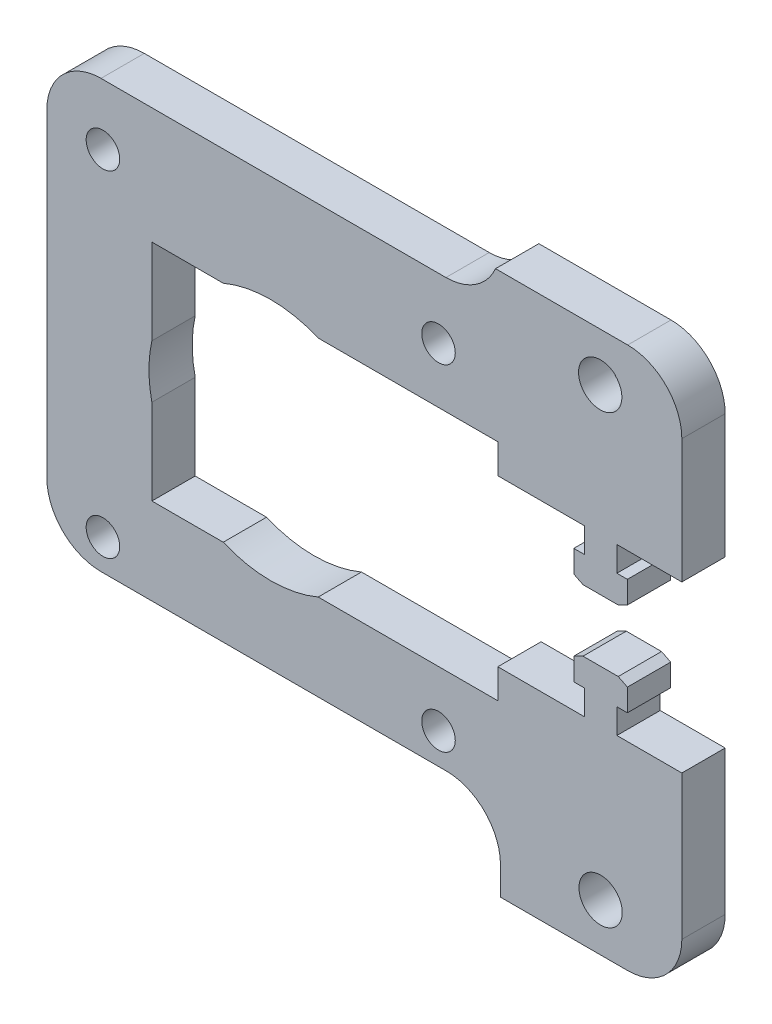
SolidWorks part; units mm, degrees
ref_plane "Front Plane" through (0, 0, 0) normal (0, 0, 1) x (1, 0, 0)
ref_plane "Top Plane" through (0, 0, 0) normal (0, 1, 0) x (1, 0, 0)
ref_plane "Right Plane" through (0, 0, 0) normal (1, 0, 0) x (0, 0, -1)
sketch "Sketch1" plane through (0, 0, 0) normal (0, 0, 1) x (1, 0, 0)
  line L0 (-6.8986, 24.1765) -> (-6.8986, 21.8765)
  line L1 (-6.8986, 21.8765) -> (-14.8986, 21.8765)
  line L2 (-14.8986, 21.8765) -> (-14.8986, 19.1565)
  line L4 (2.1014, 11.1565) -> (2.1014, 21.8765)
  line L7 (-3.8986, 24.1765) -> (-2.9286, 24.1765)
  line L8 (-2.9286, 24.1765) -> (-2.9286, 26.2329)
  line L9 (-2.9286, 26.2329) -> (-3.7758, 26.6565)
  line L10 (-3.7758, 26.6565) -> (-7.0314, 26.6565)
  line L11 (-7.0314, 26.6565) -> (-7.8786, 26.2329)
  line L12 (-7.8786, 26.2329) -> (-7.8786, 24.1765)
  line L13 (-7.8786, 24.1765) -> (-6.8986, 24.1765)
  line L14 (-56.5588, 11.1565) -> (2.1014, 11.1565)
  line L17 (-14.8986, 19.1565) -> (-46.857, 19.1565)
  line L18 (-56.5588, 11.1565) -> (-56.5588, 19.1565)
  line L19 (-3.8986, 24.1765) -> (-3.8986, 21.8765)
  line L20 (-3.8986, 21.8765) -> (2.1014, 21.8765)
  line L21 (2.1014, 29.5165) -> (-53.6577, 29.5165) construction
  line L22 (-7.8786, 34.8565) -> (-6.8986, 34.8565)
  line L23 (-7.8786, 32.8001) -> (-7.8786, 34.8565)
  line L24 (-7.0314, 32.3765) -> (-7.8786, 32.8001)
  line L25 (-3.7758, 32.3765) -> (-7.0314, 32.3765)
  line L26 (-2.9286, 32.8001) -> (-3.7758, 32.3765)
  line L27 (-2.9286, 34.8565) -> (-2.9286, 32.8001)
  line L28 (-3.8986, 37.1565) -> (2.1014, 37.1565)
  line L29 (-3.8986, 34.8565) -> (-3.8986, 37.1565)
  line L30 (-3.8986, 34.8565) -> (-2.9286, 34.8565)
  line L31 (-6.8986, 37.1565) -> (-14.8986, 37.1565)
  line L32 (-6.8986, 34.8565) -> (-6.8986, 37.1565)
  line L33 (-56.5588, 47.8765) -> (-56.5588, 39.8765)
  line L34 (-14.8986, 39.8765) -> (-46.857, 39.8765)
  line L36 (2.1014, 47.8765) -> (2.1014, 37.1565)
  line L37 (-14.8986, 37.1565) -> (-14.8986, 39.8765)
  line L38 (-56.5588, 47.8765) -> (-56.5588, 50.6194)
  line L39 (-56.5588, 50.6194) -> (2.1014, 50.6194)
  line L40 (2.1014, 50.6194) -> (2.1014, 47.8765)
  line L41 (-56.5588, 39.8765) -> (-56.5588, 19.1565)
  line L42 (-46.857, 39.8765) -> (-46.857, 19.1565)
  circle A0 centre (-51.3786, 14.0165) radius 1.55
  circle A1 centre (-20.3786, 14.0165) radius 1.55
  circle A4 centre (-51.3786, 45.0165) radius 1.55
  circle A5 centre (-20.3786, 45.0165) radius 1.55
  dimension "D12" = 3.1
  dimension "D13" = 3.1
  dimension "D14" = 31
  dimension "D16" = 15.5
  dimension "D15" = 15.5
  dimension "D21" = 11.1565
  dimension "D19" = 3.1
  dimension "D23" = 3.1
  dimension "D26" = 31
  dimension "D2" = 2.48
  dimension "D3" = 206.565
  dimension "D4" = 206.565
  dimension "D5" = 4.95
  dimension "D6" = 90
  dimension "D7" = 8
  dimension "D8" = 90
  dimension "D9" = 6
  dimension "D10" = 2.3
  dimension "D11" = 2.86
  dimension "D22" = 2.1014
extrude "Boss-Extrude1" add sketch "Sketch1" along normal blind 4
sketch "Sketch2" plane through (0, 0, 4) normal (0, 0, 1) x (1, 0, 0)
  line L0 (-51.3786, 45.0165) -> (-20.3786, 14.0165) construction
  circle A0 centre (-35.8786, 29.5165) radius 11.25
  dimension "D1" = 22.5
extrude "Cut-Extrude1" cut sketch "Sketch2" against normal blind 10
sketch "Sketch4" plane through (0, 0, 0) normal (0, 0, -1) x (-1, 0, 0)
  line L0 (5.4036, 32.3765) -> (5.4036, 53.6194) construction
  line L2 (-2.1014, 50.6194) -> (-2.1014, 53.6194)
  line L3 (-2.1014, 53.6194) -> (15.1092, 53.6194)
  line L4 (15.1092, 50.6194) -> (15.1092, 53.6194)
  line L6 (-2.1014, 11.1565) -> (-2.1014, 3.5631)
  line L7 (-2.1014, 3.5631) -> (14.6532, 3.5631)
  line L8 (14.6532, 11.1565) -> (14.6532, 3.5631)
  line L9 (7.0314, 32.3765) -> (3.7758, 32.3765) construction
  line L10 (5.4036, 26.6565) -> (5.4036, 3.5631) construction
  line L11 (3.7758, 26.6565) -> (7.0314, 26.6565) construction
  line L12 (-2.1014, 50.6194) -> (-2.1014, 46.0343)
  line L13 (-2.1014, 37.1565) -> (-2.1014, 50.6194) construction
  line L14 (-2.1014, 46.0343) -> (15.1092, 46.213)
  line L15 (15.1092, 46.213) -> (15.1092, 50.6194)
  line L16 (-2.1014, 11.1565) -> (14.6532, 11.1565)
  circle A0 centre (5.4036, 49.1753) radius 2
  circle A1 centre (5.4036, 7.9565) radius 2
  dimension "D2" = 4
  dimension "D3" = 4
extrude "Boss-Extrude2" add sketch "Sketch4" against normal up to surface (4 mm away) up to face at (-15.883, 29.6608, 4)
sketch "Sketch5" plane through (0, 0, 0) normal (0, 0, -1) x (-1, 0, 0)
  circle A0 centre (5.4403, 49.1662) radius 2.0018
extrude "Cut-Extrude2" cut sketch "Sketch5" against normal through all
fillet "Fillet1" radius 5 6 edges at (2.1014, 53.6194, 2) (2.1014, 3.5631, 2) (-56.5588, 11.1565, 2) (-56.5588, 50.6194, 2) (-14.6532, 11.1565, 2) (-15.1092, 50.6194, 2)
